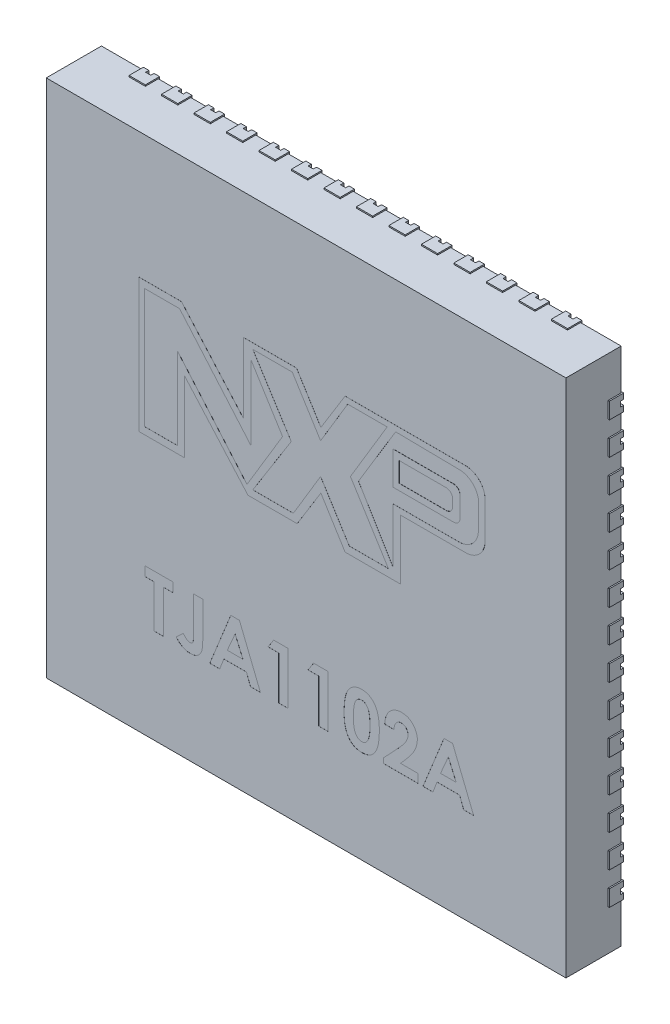
SolidWorks part; units mm, degrees
ref_plane "Front Plane" through (0, 0, 0) normal (0, 0, 1) x (1, 0, 0)
ref_plane "Top Plane" through (0, 0, 0) normal (0, 1, 0) x (1, 0, 0)
ref_plane "Right Plane" through (0, 0, 0) normal (1, 0, 0) x (0, 0, -1)
sketch "Sketch1" plane through (0, 0, 0) normal (0, 0, 1) x (1, 0, 0)
  line L1 (4, -4) -> (-4, -4)
  line L2 (4, -4) -> (4, 4)
  line L3 (4, 4) -> (-4, 4)
  line L4 (-4, -4) -> (-4, 4)
  line L5 (4, -4) -> (-4, 4) construction
  line L6 (4, 4) -> (-4, -4) construction
  point P0 (0, 0)
  dimension "D1" = 8
  dimension "D2" = 8
extrude "Boss-Extrude1" add sketch "Sketch1" along normal blind 0.85
sketch "Sketch3" plane through (0, 0, 0.85) normal (0, 0, 1) x (1, 0, 0)
  line L1 (-1.8824, 1.9808) -> (1.8824, 1.9808)
  line L2 (-1.8824, 1.9808) -> (-1.8824, -1.9808)
  line L3 (-1.8824, -1.9808) -> (1.8824, -1.9808)
  line L4 (1.8824, 1.9808) -> (1.8824, -1.9808)
  line L5 (-1.8824, 1.9808) -> (1.8824, -1.9808) construction
  line L6 (-1.8824, -1.9808) -> (1.8824, 1.9808) construction
  point P0 (0, 0)
sketch "Sketch4" plane through (0, 0, 0) normal (0, 0, -1) x (-1, 0, 0)
  line L5 (2.5, 2.25) -> (2.5, 2.1354)
  line L6 (-2.25, 2.5) -> (2.25, 2.5)
  line L11 (-2.5, 2.25) -> (-2.5, -2.25)
  line L12 (-2.25, -2.5) -> (2.25, -2.5)
  line L14 (-2.5, 2.5) -> (2.5, -2.5) construction
  line L15 (-2.5, -2.5) -> (2.5, 2.5) construction
  line L16 (2.5, 1.4646) -> (2.5, -2.25)
  arc A7 (2.25, -2.5) -> (2.5, -2.25) centre (2.25, -2.25) ccw
  arc A8 (-2.5, -2.25) -> (-2.25, -2.5) centre (-2.25, -2.25) ccw
  arc A9 (2.25, 2.5) -> (2.5, 2.25) centre (2.25, 2.25) cw
  arc A10 (-2.5, 2.25) -> (-2.25, 2.5) centre (-2.25, 2.25) cw
  arc A11 (2.4286, 2.0396) -> (2.4286, 1.5604) centre (2.5, 1.8) ccw
  arc A12 (2.5, 2.1354) -> (2.4286, 2.0396) centre (2.4, 2.1354) cw
  arc A13 (2.4286, 1.5604) -> (2.5, 1.4646) centre (2.4, 1.4646) cw
  point P0 (0, 0)
  point P23 (2.5, 2.05)
  dimension "D3" = 0.25
  dimension "D4" = 0.2
  dimension "D5" = 0.25
  dimension "D6" = 0.1
  dimension "D1" = 5
  dimension "D2" = 5
sketch "Sketch6" plane through (0, 0, 0.85) normal (0, 0, 1) x (1, 0, 0)
  line L0 (70.7212, 256.7277) -> (518.7212, 256.7277) construction
  line L1 (-2.5722, 0) -> (-2.5722, 2.0583)
  line L2 (-2.5722, 2.0583) -> (-1.9179, 2.0583)
  line L3 (-1.9179, 2.0583) -> (-0.9614, 0.9766)
  line L4 (-0.9614, 0.9766) -> (-0.9614, 2.0583)
  line L5 (-0.9614, 2.0583) -> (-0.1462, 2.0583)
  line L6 (-0.1462, 2.0583) -> (0.2284, 1.4545)
  line L7 (0.2284, 1.4545) -> (0.6013, 2.0583)
  line L8 (0.6013, 2.0583) -> (2.4559, 2.0583)
  line L9 (2.7559, 1.7583) -> (2.7559, 1.199)
  line L10 (2.4559, 0.899) -> (1.4554, 0.899)
  line L11 (1.4554, 0.899) -> (1.4554, -0.0211)
  line L12 (1.4554, -0.0211) -> (0.6013, -0.0211)
  line L13 (0.6013, -0.0211) -> (0.2284, 0.5802)
  line L14 (0.2284, 0.5802) -> (-0.1364, -0.0105)
  line L15 (-0.1364, -0.0105) -> (-0.8934, -0.0105)
  line L16 (-0.8934, -0.0105) -> (-1.8737, 1.0981)
  line L17 (-1.8737, 1.0981) -> (-1.8737, 0)
  line L18 (-1.8737, 0) -> (-2.5722, 0)
  line L19 (-2.4846, 0.1087) -> (-2.4846, 1.9505)
  line L20 (-2.4846, 1.9505) -> (-1.9464, 1.9505)
  line L21 (-1.9464, 1.9505) -> (-0.8502, 0.6771)
  line L22 (-0.8502, 0.6771) -> (-0.8502, 1.8218)
  line L23 (-0.8502, 1.8218) -> (-0.3611, 1.0381)
  line L24 (-0.3611, 1.0381) -> (-0.9093, 0.1258)
  line L25 (-0.9093, 0.1258) -> (-1.9778, 1.3671)
  line L26 (-1.9778, 1.3671) -> (-1.9778, 0.1087)
  line L27 (-1.9778, 0.1087) -> (-2.4846, 0.1087)
  line L28 (-0.8199, 1.9719) -> (-0.2112, 1.9719)
  line L29 (-0.2112, 1.9719) -> (0.224, 1.2753)
  line L30 (0.224, 1.2753) -> (0.6416, 1.9719)
  line L31 (0.6416, 1.9719) -> (1.2491, 1.9719)
  line L32 (1.2491, 1.9719) -> (0.6835, 1.0283)
  line L33 (0.6835, 1.0283) -> (1.2684, 0.092)
  line L34 (1.2684, 0.092) -> (0.6649, 0.092)
  line L35 (0.6649, 0.092) -> (0.224, 0.7978)
  line L36 (0.224, 0.7978) -> (-0.1955, 0.0981)
  line L37 (-0.1955, 0.0981) -> (-0.8199, 0.0981)
  line L38 (-0.8199, 0.0981) -> (-0.228, 1.0381)
  line L39 (-0.228, 1.0381) -> (-0.8199, 1.9719)
  line L40 (1.3791, 1.9719) -> (2.3628, 1.9581)
  line L41 (2.6586, 1.6539) -> (2.6534, 1.2867)
  line L42 (2.3534, 0.9909) -> (1.3388, 0.9909)
  line L43 (1.3388, 0.9909) -> (1.3388, 0.1474)
  line L44 (1.3388, 0.1474) -> (0.8077, 1.0283)
  line L45 (0.8077, 1.0283) -> (1.3791, 1.9719)
  line L47 (1.3388, 1.7237) -> (2.2715, 1.7237)
  line L48 (2.3715, 1.6237) -> (2.3715, 1.3142)
  line L49 (2.2715, 1.2142) -> (1.3388, 1.2142)
  line L50 (1.3388, 1.7237) -> (1.3388, 1.2142)
  line L51 (1.4343, 1.6171) -> (2.1585, 1.6171)
  line L52 (1.4343, 1.6171) -> (1.4343, 1.3132)
  line L53 (1.4343, 1.3132) -> (2.1585, 1.3132)
  line L54 (2.2585, 1.5171) -> (2.2585, 1.4132)
  arc A0 (2.7559, 1.199) -> (2.4559, 0.899) centre (2.4559, 1.199) cw
  arc A1 (2.4559, 2.0583) -> (2.7559, 1.7583) centre (2.4559, 1.7583) cw
  arc A2 (2.6534, 1.2867) -> (2.3534, 0.9909) centre (2.3534, 1.2909) cw
  arc A3 (2.3628, 1.9581) -> (2.6586, 1.6539) centre (2.3586, 1.6581) cw
  arc A4 (2.1585, 1.3132) -> (2.2585, 1.4132) centre (2.1585, 1.4132) ccw
  arc A5 (2.1585, 1.6171) -> (2.2585, 1.5171) centre (2.1585, 1.5171) cw
  arc A6 (2.3715, 1.3142) -> (2.2715, 1.2142) centre (2.2715, 1.3142) cw
  arc A7 (2.2715, 1.7237) -> (2.3715, 1.6237) centre (2.2715, 1.6237) cw
  dimension "D1" = 0.3
  dimension "D2" = 0.3
  dimension "D3" = 0.1
extrude "Boss-Extrude2" add sketch "Sketch6" along normal blind 0.001 contours A1 L8 L7 L6 L5 L4 L3 L2 L1 L18 L17 L16 L15 L14 L13 L12 L11 L10 A0 L9 L38 L39 L28 L29 L30 L31 L32 L33 L34 L35 L36 L37 L26 L27 L19 L20 L21 L22 L23 L24 L25 L40 A3 L41 A2 L42 L43 L44 | L52 L51 A5 L54 A4 L53 | L50 L49 A6 L48 A7 L47 region at (-2.515, 1.0291, 0.85)
sketch "Sketch8" plane through (0, 0, 0.85) normal (0, 0, 1) x (1, 0, 0)
  line L0 (-2.4928, -2.5446) -> (2.0877, -2.5446) construction
  text T0 "<b>TJA1102A</b>" font "Century Gothic" height 0.8
  point P3 (-2.4928, -2.6652)
extrude "Cut-Extrude3" cut sketch "Sketch8" against normal blind 0.001
sketch "Sketch10" plane through (0, 0, 0.85) normal (0, 0, 1) x (1, 0, 0)
  line L0 (1.3388, 1.7237) -> (2.2715, 1.7237)
  line L1 (1.3388, 1.7237) -> (1.3388, 1.2142)
  line L2 (1.3388, 1.2142) -> (2.2715, 1.2142)
  line L3 (2.3715, 1.6237) -> (2.3715, 1.3142)
  line L4 (2.2585, 1.5171) -> (2.2585, 1.4132)
  line L5 (2.1585, 1.6171) -> (1.4343, 1.6171)
  line L6 (1.4343, 1.6171) -> (1.4343, 1.3132)
  line L7 (1.4343, 1.3132) -> (2.1585, 1.3132)
  line L8 (1.4343, 1.6171) -> (2.1585, 1.6171) construction
  line L9 (1.4343, 1.6171) -> (2.1585, 1.6171) construction
  arc A0 (2.2715, 1.7237) -> (2.3715, 1.6237) centre (2.2715, 1.6237) cw
  arc A1 (2.3715, 1.3142) -> (2.2715, 1.2142) centre (2.2715, 1.3142) cw
  arc A2 (2.2585, 1.4132) -> (2.1585, 1.3132) centre (2.1585, 1.4132) cw
  arc A3 (2.1585, 1.6171) -> (2.2585, 1.5171) centre (2.1585, 1.5171) cw
  point P26 (1.4343, 1.6171)
extrude "Boss-Extrude3" add sketch "Sketch10" along normal blind 0.002
sketch "Sketch17" plane through (0, 4, 0) normal (0, 1, 0) x (1, 0, 0)
  line L0 (0, 0) -> (0, 0.4871) construction
  line L1 (-2.8779, -0.0822) -> (-2.775, -0.0822)
  line L2 (-2.8779, -0.0822) -> (-2.8779, -0.1355)
  line L3 (-2.8779, -0.1355) -> (-2.775, -0.1355)
  line L4 (-2.775, -0.0822) -> (-2.775, -0.1355)
  line L5 (2.775, -0.0822) -> (2.775, -0.1355)
  line L6 (2.8779, -0.1355) -> (2.775, -0.1355)
  line L7 (2.8779, -0.0822) -> (2.8779, -0.1355)
  line L8 (2.8779, -0.0822) -> (2.775, -0.0822)
extrude "Boss-Extrude7" add sketch "Sketch17" along normal blind 0.01
mirror "Mirror3" about plane through (0, 0, 0) normal (0, 1, 0) of "Boss-Extrude7"
sketch "Sketch18" plane through (-4, 0, 0) normal (-1, 0, 0) x (0, 0, 1)
  line L0 (0, 0) -> (0.2423, 0) construction
  line L1 (0.0822, -2.6954) -> (0.1355, -2.6954)
  line L2 (0.0822, -2.6954) -> (0.0822, -2.7925)
  line L3 (0.0822, -2.7925) -> (0.1355, -2.7925)
  line L4 (0.1355, -2.6954) -> (0.1355, -2.7925)
  line L5 (0.1355, 2.6954) -> (0.1355, 2.7925)
  line L6 (0.0822, 2.7925) -> (0.1355, 2.7925)
  line L7 (0.0822, 2.6954) -> (0.0822, 2.7925)
  line L8 (0.0822, 2.6954) -> (0.1355, 2.6954)
  line L9 (0.1355, 4.01) -> (0.1355, 4) construction
  line L10 (0.0822, 4.01) -> (0.0822, 4) construction
  dimension "D1" = 0
  dimension "D2" = 0
extrude "Boss-Extrude8" add sketch "Sketch18" along normal blind 0.01
mirror "Mirror4" about plane through (0, 0, 0) normal (1, 0, 0) of "Boss-Extrude8"
extrude "Boss-Extrude11" add sketch "Sketch4" along normal blind 0.02
sketch "Sketch19" plane through (0, 0, 0) normal (0, 0, -1) x (-1, 0, 0)
  line L0 (-3.25, 4.375) -> (-3.25, 3.625) construction
  line L1 (-4, 4) -> (4, 4) construction
  line L2 (-3.125, 4.375) -> (-3.125, 3.625)
  line L3 (-3.375, 4.375) -> (-3.375, 3.625)
  line L4 (-2.875, 4.375) -> (-2.875, 3.625)
  line L5 (-2.625, 4.375) -> (-2.625, 3.625)
  line L6 (-2.75, 4.375) -> (-2.75, 3.625) construction
  line L7 (-2.375, 4.375) -> (-2.375, 3.625)
  line L8 (-2.125, 4.375) -> (-2.125, 3.625)
  line L9 (-2.25, 4.375) -> (-2.25, 3.625) construction
  line L10 (-1.875, 4.375) -> (-1.875, 3.625)
  line L11 (-1.625, 4.375) -> (-1.625, 3.625)
  line L12 (-1.75, 4.375) -> (-1.75, 3.625) construction
  line L13 (-1.375, 4.375) -> (-1.375, 3.625)
  line L14 (-1.125, 4.375) -> (-1.125, 3.625)
  line L15 (-1.25, 4.375) -> (-1.25, 3.625) construction
  line L16 (-0.875, 4.375) -> (-0.875, 3.625)
  line L17 (-0.625, 4.375) -> (-0.625, 3.625)
  line L18 (-0.75, 4.375) -> (-0.75, 3.625) construction
  line L19 (-0.375, 4.375) -> (-0.375, 3.625)
  line L20 (-0.125, 4.375) -> (-0.125, 3.625)
  line L21 (-0.25, 4.375) -> (-0.25, 3.625) construction
  line L22 (0.125, 4.375) -> (0.125, 3.625)
  line L23 (0.375, 4.375) -> (0.375, 3.625)
  line L24 (0.25, 4.375) -> (0.25, 3.625) construction
  line L25 (0.625, 4.375) -> (0.625, 3.625)
  line L26 (0.875, 4.375) -> (0.875, 3.625)
  line L27 (0.75, 4.375) -> (0.75, 3.625) construction
  line L28 (1.125, 4.375) -> (1.125, 3.625)
  line L29 (1.375, 4.375) -> (1.375, 3.625)
  line L30 (1.25, 4.375) -> (1.25, 3.625) construction
  line L31 (1.625, 4.375) -> (1.625, 3.625)
  line L32 (1.875, 4.375) -> (1.875, 3.625)
  line L33 (1.75, 4.375) -> (1.75, 3.625) construction
  line L34 (2.125, 4.375) -> (2.125, 3.625)
  line L35 (2.375, 4.375) -> (2.375, 3.625)
  line L36 (2.25, 4.375) -> (2.25, 3.625) construction
  line L37 (2.625, 4.375) -> (2.625, 3.625)
  line L38 (2.875, 4.375) -> (2.875, 3.625)
  line L39 (2.75, 4.375) -> (2.75, 3.625) construction
  line L40 (3.125, 4.375) -> (3.125, 3.625)
  line L41 (3.375, 4.375) -> (3.375, 3.625)
  line L42 (3.25, 4.375) -> (3.25, 3.625) construction
  line L43 (0, 0) -> (1.75, 0) construction
  line L44 (0, 0) -> (0, 1.3207) construction
  line L45 (4.375, 3.25) -> (3.625, 3.25) construction
  line L47 (-4.375, 3.25) -> (-3.625, 3.25) construction
  line L48 (-4.375, 3.125) -> (-3.625, 3.125)
  line L49 (-4.375, 3.375) -> (-3.625, 3.375)
  line L50 (-4.375, 2.75) -> (-3.625, 2.75) construction
  line L51 (-4.375, 2.625) -> (-3.625, 2.625)
  line L52 (-4.375, 2.875) -> (-3.625, 2.875)
  line L53 (-4.375, 2.25) -> (-3.625, 2.25) construction
  line L54 (-4.375, 2.125) -> (-3.625, 2.125)
  line L55 (-4.375, 2.375) -> (-3.625, 2.375)
  line L56 (-4.375, 1.75) -> (-3.625, 1.75) construction
  line L57 (-4.375, 1.625) -> (-3.625, 1.625)
  line L58 (-4.375, 1.875) -> (-3.625, 1.875)
  line L59 (-4.375, 1.25) -> (-3.625, 1.25) construction
  line L60 (-4.375, 1.125) -> (-3.625, 1.125)
  line L61 (-4.375, 1.375) -> (-3.625, 1.375)
  line L62 (-4.375, 0.75) -> (-3.625, 0.75) construction
  line L63 (-4.375, 0.625) -> (-3.625, 0.625)
  line L64 (-4.375, 0.875) -> (-3.625, 0.875)
  line L65 (-4.375, 0.25) -> (-3.625, 0.25) construction
  line L66 (-4.375, 0.125) -> (-3.625, 0.125)
  line L67 (-4.375, 0.375) -> (-3.625, 0.375)
  line L68 (-4.375, -0.25) -> (-3.625, -0.25) construction
  line L69 (-4.375, -0.375) -> (-3.625, -0.375)
  line L70 (-4.375, -0.125) -> (-3.625, -0.125)
  line L71 (-4.375, -0.75) -> (-3.625, -0.75) construction
  line L72 (-4.375, -0.875) -> (-3.625, -0.875)
  line L73 (-4.375, -0.625) -> (-3.625, -0.625)
  line L74 (-4.375, -1.25) -> (-3.625, -1.25) construction
  line L75 (-4.375, -1.375) -> (-3.625, -1.375)
  line L76 (-4.375, -1.125) -> (-3.625, -1.125)
  line L77 (-4.375, -1.75) -> (-3.625, -1.75) construction
  line L78 (-4.375, -1.875) -> (-3.625, -1.875)
  line L79 (-4.375, -1.625) -> (-3.625, -1.625)
  line L80 (-4.375, -2.25) -> (-3.625, -2.25) construction
  line L81 (-4.375, -2.375) -> (-3.625, -2.375)
  line L82 (-4.375, -2.125) -> (-3.625, -2.125)
  line L83 (-4.375, -2.75) -> (-3.625, -2.75) construction
  line L84 (-4.375, -2.875) -> (-3.625, -2.875)
  line L85 (-4.375, -2.625) -> (-3.625, -2.625)
  line L86 (-4.375, -3.25) -> (-3.625, -3.25) construction
  line L87 (-4.375, -3.375) -> (-3.625, -3.375)
  line L88 (-4.375, -3.125) -> (-3.625, -3.125)
  line L89 (4.375, 3.125) -> (3.625, 3.125)
  line L90 (4.375, 3.375) -> (3.625, 3.375)
  line L91 (4.375, 2.75) -> (3.625, 2.75) construction
  line L92 (4.375, 2.625) -> (3.625, 2.625)
  line L93 (4.375, 2.875) -> (3.625, 2.875)
  line L94 (4.375, 2.25) -> (3.625, 2.25) construction
  line L95 (4.375, 2.125) -> (3.625, 2.125)
  line L96 (4.375, 2.375) -> (3.625, 2.375)
  line L97 (4.375, 1.75) -> (3.625, 1.75) construction
  line L98 (4.375, 1.625) -> (3.625, 1.625)
  line L99 (4.375, 1.875) -> (3.625, 1.875)
  line L100 (4.375, 1.25) -> (3.625, 1.25) construction
  line L101 (4.375, 1.125) -> (3.625, 1.125)
  line L102 (4.375, 1.375) -> (3.625, 1.375)
  line L103 (4.375, 0.75) -> (3.625, 0.75) construction
  line L104 (4.375, 0.625) -> (3.625, 0.625)
  line L105 (4.375, 0.875) -> (3.625, 0.875)
  line L106 (4.375, 0.25) -> (3.625, 0.25) construction
  line L107 (4.375, 0.125) -> (3.625, 0.125)
  line L108 (4.375, 0.375) -> (3.625, 0.375)
  line L109 (4.375, -0.25) -> (3.625, -0.25) construction
  line L110 (4.375, -0.375) -> (3.625, -0.375)
  line L111 (4.375, -0.125) -> (3.625, -0.125)
  line L112 (4.375, -0.75) -> (3.625, -0.75) construction
  line L113 (4.375, -0.875) -> (3.625, -0.875)
  line L114 (4.375, -0.625) -> (3.625, -0.625)
  line L115 (4.375, -1.25) -> (3.625, -1.25) construction
  line L116 (4.375, -1.375) -> (3.625, -1.375)
  line L117 (4.375, -1.125) -> (3.625, -1.125)
  line L118 (4.375, -1.75) -> (3.625, -1.75) construction
  line L119 (4.375, -1.875) -> (3.625, -1.875)
  line L120 (4.375, -1.625) -> (3.625, -1.625)
  line L121 (4.375, -2.25) -> (3.625, -2.25) construction
  line L122 (4.375, -2.375) -> (3.625, -2.375)
  line L123 (4.375, -2.125) -> (3.625, -2.125)
  line L124 (4.375, -2.75) -> (3.625, -2.75) construction
  line L125 (4.375, -2.875) -> (3.625, -2.875)
  line L126 (4.375, -2.625) -> (3.625, -2.625)
  line L127 (4.375, -3.25) -> (3.625, -3.25) construction
  line L128 (4.375, -3.375) -> (3.625, -3.375)
  line L129 (4.375, -3.125) -> (3.625, -3.125)
  line L130 (-3.25, -4.375) -> (-3.25, -3.625) construction
  line L131 (-3.125, -4.375) -> (-3.125, -3.625)
  line L132 (-3.375, -4.375) -> (-3.375, -3.625)
  line L133 (-2.75, -4.375) -> (-2.75, -3.625) construction
  line L134 (-2.625, -4.375) -> (-2.625, -3.625)
  line L135 (-2.875, -4.375) -> (-2.875, -3.625)
  line L136 (-2.25, -4.375) -> (-2.25, -3.625) construction
  line L137 (-2.125, -4.375) -> (-2.125, -3.625)
  line L138 (-2.375, -4.375) -> (-2.375, -3.625)
  line L139 (-1.75, -4.375) -> (-1.75, -3.625) construction
  line L140 (-1.625, -4.375) -> (-1.625, -3.625)
  line L141 (-1.875, -4.375) -> (-1.875, -3.625)
  line L142 (-1.25, -4.375) -> (-1.25, -3.625) construction
  line L143 (-1.125, -4.375) -> (-1.125, -3.625)
  line L144 (-1.375, -4.375) -> (-1.375, -3.625)
  line L145 (-0.75, -4.375) -> (-0.75, -3.625) construction
  line L146 (-0.625, -4.375) -> (-0.625, -3.625)
  line L147 (-0.875, -4.375) -> (-0.875, -3.625)
  line L148 (-0.25, -4.375) -> (-0.25, -3.625) construction
  line L149 (-0.125, -4.375) -> (-0.125, -3.625)
  line L150 (-0.375, -4.375) -> (-0.375, -3.625)
  line L151 (0.25, -4.375) -> (0.25, -3.625) construction
  line L152 (0.375, -4.375) -> (0.375, -3.625)
  line L153 (0.125, -4.375) -> (0.125, -3.625)
  line L154 (0.75, -4.375) -> (0.75, -3.625) construction
  line L155 (0.875, -4.375) -> (0.875, -3.625)
  line L156 (0.625, -4.375) -> (0.625, -3.625)
  line L157 (1.25, -4.375) -> (1.25, -3.625) construction
  line L158 (1.375, -4.375) -> (1.375, -3.625)
  line L159 (1.125, -4.375) -> (1.125, -3.625)
  line L160 (1.75, -4.375) -> (1.75, -3.625) construction
  line L161 (1.875, -4.375) -> (1.875, -3.625)
  line L162 (1.625, -4.375) -> (1.625, -3.625)
  line L163 (2.25, -4.375) -> (2.25, -3.625) construction
  line L164 (2.375, -4.375) -> (2.375, -3.625)
  line L165 (2.125, -4.375) -> (2.125, -3.625)
  line L166 (2.75, -4.375) -> (2.75, -3.625) construction
  line L167 (2.875, -4.375) -> (2.875, -3.625)
  line L168 (2.625, -4.375) -> (2.625, -3.625)
  line L169 (3.25, -4.375) -> (3.25, -3.625) construction
  line L170 (3.375, -4.375) -> (3.375, -3.625)
  line L171 (3.125, -4.375) -> (3.125, -3.625)
  arc A0 (-3.125, 4.375) -> (-3.375, 4.375) centre (-3.25, 4.375) ccw
  arc A1 (-3.375, 3.625) -> (-3.125, 3.625) centre (-3.25, 3.625) ccw
  arc A2 (-2.625, 4.375) -> (-2.875, 4.375) centre (-2.75, 4.375) ccw
  arc A3 (-2.875, 3.625) -> (-2.625, 3.625) centre (-2.75, 3.625) ccw
  arc A4 (-2.125, 4.375) -> (-2.375, 4.375) centre (-2.25, 4.375) ccw
  arc A5 (-2.375, 3.625) -> (-2.125, 3.625) centre (-2.25, 3.625) ccw
  arc A6 (-1.625, 4.375) -> (-1.875, 4.375) centre (-1.75, 4.375) ccw
  arc A7 (-1.875, 3.625) -> (-1.625, 3.625) centre (-1.75, 3.625) ccw
  arc A8 (-1.125, 4.375) -> (-1.375, 4.375) centre (-1.25, 4.375) ccw
  arc A9 (-1.375, 3.625) -> (-1.125, 3.625) centre (-1.25, 3.625) ccw
  arc A10 (-0.625, 4.375) -> (-0.875, 4.375) centre (-0.75, 4.375) ccw
  arc A11 (-0.875, 3.625) -> (-0.625, 3.625) centre (-0.75, 3.625) ccw
  arc A12 (-0.125, 4.375) -> (-0.375, 4.375) centre (-0.25, 4.375) ccw
  arc A13 (-0.375, 3.625) -> (-0.125, 3.625) centre (-0.25, 3.625) ccw
  arc A14 (0.375, 4.375) -> (0.125, 4.375) centre (0.25, 4.375) ccw
  arc A15 (0.125, 3.625) -> (0.375, 3.625) centre (0.25, 3.625) ccw
  arc A16 (0.875, 4.375) -> (0.625, 4.375) centre (0.75, 4.375) ccw
  arc A17 (0.625, 3.625) -> (0.875, 3.625) centre (0.75, 3.625) ccw
  arc A18 (1.375, 4.375) -> (1.125, 4.375) centre (1.25, 4.375) ccw
  arc A19 (1.125, 3.625) -> (1.375, 3.625) centre (1.25, 3.625) ccw
  arc A20 (1.875, 4.375) -> (1.625, 4.375) centre (1.75, 4.375) ccw
  arc A21 (1.625, 3.625) -> (1.875, 3.625) centre (1.75, 3.625) ccw
  arc A22 (2.375, 4.375) -> (2.125, 4.375) centre (2.25, 4.375) ccw
  arc A23 (2.125, 3.625) -> (2.375, 3.625) centre (2.25, 3.625) ccw
  arc A24 (2.875, 4.375) -> (2.625, 4.375) centre (2.75, 4.375) ccw
  arc A25 (2.625, 3.625) -> (2.875, 3.625) centre (2.75, 3.625) ccw
  arc A26 (3.375, 4.375) -> (3.125, 4.375) centre (3.25, 4.375) ccw
  arc A27 (3.125, 3.625) -> (3.375, 3.625) centre (3.25, 3.625) ccw
  arc A28 (-4.375, 3.125) -> (-4.375, 3.375) centre (-4.375, 3.25) cw
  arc A29 (-3.625, 3.375) -> (-3.625, 3.125) centre (-3.625, 3.25) cw
  arc A30 (-4.375, 2.625) -> (-4.375, 2.875) centre (-4.375, 2.75) cw
  arc A31 (-3.625, 2.875) -> (-3.625, 2.625) centre (-3.625, 2.75) cw
  arc A32 (-4.375, 2.125) -> (-4.375, 2.375) centre (-4.375, 2.25) cw
  arc A33 (-3.625, 2.375) -> (-3.625, 2.125) centre (-3.625, 2.25) cw
  arc A34 (-4.375, 1.625) -> (-4.375, 1.875) centre (-4.375, 1.75) cw
  arc A35 (-3.625, 1.875) -> (-3.625, 1.625) centre (-3.625, 1.75) cw
  arc A36 (-4.375, 1.125) -> (-4.375, 1.375) centre (-4.375, 1.25) cw
  arc A37 (-3.625, 1.375) -> (-3.625, 1.125) centre (-3.625, 1.25) cw
  arc A38 (-4.375, 0.625) -> (-4.375, 0.875) centre (-4.375, 0.75) cw
  arc A39 (-3.625, 0.875) -> (-3.625, 0.625) centre (-3.625, 0.75) cw
  arc A40 (-4.375, 0.125) -> (-4.375, 0.375) centre (-4.375, 0.25) cw
  arc A41 (-3.625, 0.375) -> (-3.625, 0.125) centre (-3.625, 0.25) cw
  arc A42 (-4.375, -0.375) -> (-4.375, -0.125) centre (-4.375, -0.25) cw
  arc A43 (-3.625, -0.125) -> (-3.625, -0.375) centre (-3.625, -0.25) cw
  arc A44 (-4.375, -0.875) -> (-4.375, -0.625) centre (-4.375, -0.75) cw
  arc A45 (-3.625, -0.625) -> (-3.625, -0.875) centre (-3.625, -0.75) cw
  arc A46 (-4.375, -1.375) -> (-4.375, -1.125) centre (-4.375, -1.25) cw
  arc A47 (-3.625, -1.125) -> (-3.625, -1.375) centre (-3.625, -1.25) cw
  arc A48 (-4.375, -1.875) -> (-4.375, -1.625) centre (-4.375, -1.75) cw
  arc A49 (-3.625, -1.625) -> (-3.625, -1.875) centre (-3.625, -1.75) cw
  arc A50 (-4.375, -2.375) -> (-4.375, -2.125) centre (-4.375, -2.25) cw
  arc A51 (-3.625, -2.125) -> (-3.625, -2.375) centre (-3.625, -2.25) cw
  arc A52 (-4.375, -2.875) -> (-4.375, -2.625) centre (-4.375, -2.75) cw
  arc A53 (-3.625, -2.625) -> (-3.625, -2.875) centre (-3.625, -2.75) cw
  arc A54 (-4.375, -3.375) -> (-4.375, -3.125) centre (-4.375, -3.25) cw
  arc A55 (-3.625, -3.125) -> (-3.625, -3.375) centre (-3.625, -3.25) cw
  arc A56 (4.375, 3.125) -> (4.375, 3.375) centre (4.375, 3.25) ccw
  arc A57 (3.625, 3.375) -> (3.625, 3.125) centre (3.625, 3.25) ccw
  arc A58 (4.375, 2.625) -> (4.375, 2.875) centre (4.375, 2.75) ccw
  arc A59 (3.625, 2.875) -> (3.625, 2.625) centre (3.625, 2.75) ccw
  arc A60 (4.375, 2.125) -> (4.375, 2.375) centre (4.375, 2.25) ccw
  arc A61 (3.625, 2.375) -> (3.625, 2.125) centre (3.625, 2.25) ccw
  arc A62 (4.375, 1.625) -> (4.375, 1.875) centre (4.375, 1.75) ccw
  arc A63 (3.625, 1.875) -> (3.625, 1.625) centre (3.625, 1.75) ccw
  arc A64 (4.375, 1.125) -> (4.375, 1.375) centre (4.375, 1.25) ccw
  arc A65 (3.625, 1.375) -> (3.625, 1.125) centre (3.625, 1.25) ccw
  arc A66 (4.375, 0.625) -> (4.375, 0.875) centre (4.375, 0.75) ccw
  arc A67 (3.625, 0.875) -> (3.625, 0.625) centre (3.625, 0.75) ccw
  arc A68 (4.375, 0.125) -> (4.375, 0.375) centre (4.375, 0.25) ccw
  arc A69 (3.625, 0.375) -> (3.625, 0.125) centre (3.625, 0.25) ccw
  arc A70 (4.375, -0.375) -> (4.375, -0.125) centre (4.375, -0.25) ccw
  arc A71 (3.625, -0.125) -> (3.625, -0.375) centre (3.625, -0.25) ccw
  arc A72 (4.375, -0.875) -> (4.375, -0.625) centre (4.375, -0.75) ccw
  arc A73 (3.625, -0.625) -> (3.625, -0.875) centre (3.625, -0.75) ccw
  arc A74 (4.375, -1.375) -> (4.375, -1.125) centre (4.375, -1.25) ccw
  arc A75 (3.625, -1.125) -> (3.625, -1.375) centre (3.625, -1.25) ccw
  arc A76 (4.375, -1.875) -> (4.375, -1.625) centre (4.375, -1.75) ccw
  arc A77 (3.625, -1.625) -> (3.625, -1.875) centre (3.625, -1.75) ccw
  arc A78 (4.375, -2.375) -> (4.375, -2.125) centre (4.375, -2.25) ccw
  arc A79 (3.625, -2.125) -> (3.625, -2.375) centre (3.625, -2.25) ccw
  arc A80 (4.375, -2.875) -> (4.375, -2.625) centre (4.375, -2.75) ccw
  arc A81 (3.625, -2.625) -> (3.625, -2.875) centre (3.625, -2.75) ccw
  arc A82 (4.375, -3.375) -> (4.375, -3.125) centre (4.375, -3.25) ccw
  arc A83 (3.625, -3.125) -> (3.625, -3.375) centre (3.625, -3.25) ccw
  arc A84 (-3.125, -4.375) -> (-3.375, -4.375) centre (-3.25, -4.375) cw
  arc A85 (-3.375, -3.625) -> (-3.125, -3.625) centre (-3.25, -3.625) cw
  arc A86 (-2.625, -4.375) -> (-2.875, -4.375) centre (-2.75, -4.375) cw
  arc A87 (-2.875, -3.625) -> (-2.625, -3.625) centre (-2.75, -3.625) cw
  arc A88 (-2.125, -4.375) -> (-2.375, -4.375) centre (-2.25, -4.375) cw
  arc A89 (-2.375, -3.625) -> (-2.125, -3.625) centre (-2.25, -3.625) cw
  arc A90 (-1.625, -4.375) -> (-1.875, -4.375) centre (-1.75, -4.375) cw
  arc A91 (-1.875, -3.625) -> (-1.625, -3.625) centre (-1.75, -3.625) cw
  arc A92 (-1.125, -4.375) -> (-1.375, -4.375) centre (-1.25, -4.375) cw
  arc A93 (-1.375, -3.625) -> (-1.125, -3.625) centre (-1.25, -3.625) cw
  arc A94 (-0.625, -4.375) -> (-0.875, -4.375) centre (-0.75, -4.375) cw
  arc A95 (-0.875, -3.625) -> (-0.625, -3.625) centre (-0.75, -3.625) cw
  arc A96 (-0.125, -4.375) -> (-0.375, -4.375) centre (-0.25, -4.375) cw
  arc A97 (-0.375, -3.625) -> (-0.125, -3.625) centre (-0.25, -3.625) cw
  arc A98 (0.375, -4.375) -> (0.125, -4.375) centre (0.25, -4.375) cw
  arc A99 (0.125, -3.625) -> (0.375, -3.625) centre (0.25, -3.625) cw
  arc A100 (0.875, -4.375) -> (0.625, -4.375) centre (0.75, -4.375) cw
  arc A101 (0.625, -3.625) -> (0.875, -3.625) centre (0.75, -3.625) cw
  arc A102 (1.375, -4.375) -> (1.125, -4.375) centre (1.25, -4.375) cw
  arc A103 (1.125, -3.625) -> (1.375, -3.625) centre (1.25, -3.625) cw
  arc A104 (1.875, -4.375) -> (1.625, -4.375) centre (1.75, -4.375) cw
  arc A105 (1.625, -3.625) -> (1.875, -3.625) centre (1.75, -3.625) cw
  arc A106 (2.375, -4.375) -> (2.125, -4.375) centre (2.25, -4.375) cw
  arc A107 (2.125, -3.625) -> (2.375, -3.625) centre (2.25, -3.625) cw
  arc A108 (2.875, -4.375) -> (2.625, -4.375) centre (2.75, -4.375) cw
  arc A109 (2.625, -3.625) -> (2.875, -3.625) centre (2.75, -3.625) cw
  arc A110 (3.375, -4.375) -> (3.125, -4.375) centre (3.25, -4.375) cw
  arc A111 (3.125, -3.625) -> (3.375, -3.625) centre (3.25, -3.625) cw
  point P4 (-3.25, 4)
  point P9 (-3.25, 3.5)
  point P15 (-2.75, 4)
  point P22 (-2.25, 4)
  point P29 (-1.75, 4)
  point P36 (-1.25, 4)
  point P43 (-0.75, 4)
  point P50 (-0.25, 4)
  point P57 (0.25, 4)
  point P64 (0.75, 4)
  point P71 (1.25, 4)
  point P78 (1.75, 4)
  point P85 (2.25, 4)
  point P92 (2.75, 4)
  point P99 (3.25, 4)
  point P108 (4, 3.25)
  point P112 (-4, 3.25)
  point P119 (-4, 2.75)
  point P126 (-4, 2.25)
  point P133 (-4, 1.75)
  point P140 (-4, 1.25)
  point P147 (-4, 0.75)
  point P154 (-4, 0.25)
  point P161 (-4, -0.25)
  point P168 (-4, -0.75)
  point P175 (-4, -1.25)
  point P182 (-4, -1.75)
  point P189 (-4, -2.25)
  point P196 (-4, -2.75)
  point P203 (-4, -3.25)
  point P213 (4, 2.75)
  point P220 (4, 2.25)
  point P227 (4, 1.75)
  point P234 (4, 1.25)
  point P241 (4, 0.75)
  point P248 (4, 0.25)
  point P255 (4, -0.25)
  point P262 (4, -0.75)
  point P269 (4, -1.25)
  point P276 (4, -1.75)
  point P283 (4, -2.25)
  point P290 (4, -2.75)
  point P297 (4, -3.25)
  point P304 (-3.25, -4)
  point P311 (-2.75, -4)
  point P318 (-2.25, -4)
  point P325 (-1.75, -4)
  point P332 (-1.25, -4)
  point P339 (-0.75, -4)
  point P346 (-0.25, -4)
  point P353 (0.25, -4)
  point P360 (0.75, -4)
  point P367 (1.25, -4)
  point P374 (1.75, -4)
  point P381 (2.25, -4)
  point P388 (2.75, -4)
  point P395 (3.25, -4)
  dimension "D1" = 0.25
  dimension "D2" = 0.5
  dimension "D3" = 3.25
  dimension "D4" = 14
extrude "Boss-Extrude12" add sketch "Sketch19" along normal blind 0.02
sketch "Sketch20" plane through (0, 0, 0.85) normal (0, 0, 1) x (1, 0, 0)
  line L1 (-4, 4) -> (4, 4)
  line L2 (-4, 4) -> (-4, -4)
  line L3 (-4, -4) -> (4, -4)
  line L4 (4, 4) -> (4, -4)
  line L5 (-5.8606, 5.4088) -> (5.2055, 5.4088)
  line L6 (-5.8606, 5.4088) -> (-5.8606, -5.1245)
  line L7 (-5.8606, -5.1245) -> (5.2055, -5.1245)
  line L8 (5.2055, 5.4088) -> (5.2055, -5.1245)
extrude "Cut-Extrude5" cut sketch "Sketch20" against normal blind 60.02
sketch "Sketch21" plane through (0, -4, 0) normal (0, -1, 0) x (1, 0, 0)
  line L0 (-3.125, -0.02) -> (-3.125, 0) construction
  line L1 (-3.375, -0.02) -> (-3.125, -0.02)
  line L2 (-3.375, -0.02) -> (-3.375, 0.2)
  line L3 (-3.375, 0.2) -> (-3.125, 0.2)
  line L4 (-3.125, -0.02) -> (-3.125, 0.2)
  line L5 (-3.125, 0) -> (-2.875, 0) construction
  line L6 (-2.875, -0.02) -> (-2.875, 0.2)
  line L7 (-2.875, -0.02) -> (-2.625, -0.02)
  line L8 (-2.625, -0.02) -> (-2.625, 0.2)
  line L9 (-2.875, 0.2) -> (-2.625, 0.2)
  line L10 (-2.375, -0.02) -> (-2.375, 0.2)
  line L11 (-2.375, -0.02) -> (-2.125, -0.02)
  line L12 (-2.125, -0.02) -> (-2.125, 0.2)
  line L13 (-2.375, 0.2) -> (-2.125, 0.2)
  line L14 (-1.875, -0.02) -> (-1.875, 0.2)
  line L15 (-1.875, -0.02) -> (-1.625, -0.02)
  line L16 (-1.625, -0.02) -> (-1.625, 0.2)
  line L17 (-1.875, 0.2) -> (-1.625, 0.2)
  line L18 (-1.375, -0.02) -> (-1.375, 0.2)
  line L19 (-1.375, -0.02) -> (-1.125, -0.02)
  line L20 (-1.125, -0.02) -> (-1.125, 0.2)
  line L21 (-1.375, 0.2) -> (-1.125, 0.2)
  line L22 (-0.875, -0.02) -> (-0.875, 0.2)
  line L23 (-0.875, -0.02) -> (-0.625, -0.02)
  line L24 (-0.625, -0.02) -> (-0.625, 0.2)
  line L25 (-0.875, 0.2) -> (-0.625, 0.2)
  line L26 (-0.375, -0.02) -> (-0.375, 0.2)
  line L27 (-0.375, -0.02) -> (-0.125, -0.02)
  line L28 (-0.125, -0.02) -> (-0.125, 0.2)
  line L29 (-0.375, 0.2) -> (-0.125, 0.2)
  line L30 (0.125, -0.02) -> (0.125, 0.2)
  line L31 (0.125, -0.02) -> (0.375, -0.02)
  line L32 (0.375, -0.02) -> (0.375, 0.2)
  line L33 (0.125, 0.2) -> (0.375, 0.2)
  line L34 (0.625, -0.02) -> (0.625, 0.2)
  line L35 (0.625, -0.02) -> (0.875, -0.02)
  line L36 (0.875, -0.02) -> (0.875, 0.2)
  line L37 (0.625, 0.2) -> (0.875, 0.2)
  line L38 (1.125, -0.02) -> (1.125, 0.2)
  line L39 (1.125, -0.02) -> (1.375, -0.02)
  line L40 (1.375, -0.02) -> (1.375, 0.2)
  line L41 (1.125, 0.2) -> (1.375, 0.2)
  line L42 (1.625, -0.02) -> (1.625, 0.2)
  line L43 (1.625, -0.02) -> (1.875, -0.02)
  line L44 (1.875, -0.02) -> (1.875, 0.2)
  line L45 (1.625, 0.2) -> (1.875, 0.2)
  line L46 (2.125, -0.02) -> (2.125, 0.2)
  line L47 (2.125, -0.02) -> (2.375, -0.02)
  line L48 (2.375, -0.02) -> (2.375, 0.2)
  line L49 (2.125, 0.2) -> (2.375, 0.2)
  line L50 (2.625, -0.02) -> (2.625, 0.2)
  line L51 (2.625, -0.02) -> (2.875, -0.02)
  line L52 (2.875, -0.02) -> (2.875, 0.2)
  line L53 (2.625, 0.2) -> (2.875, 0.2)
  line L54 (3.125, -0.02) -> (3.125, 0.2)
  line L55 (3.125, -0.02) -> (3.375, -0.02)
  line L56 (3.375, -0.02) -> (3.375, 0.2)
  line L57 (3.125, 0.2) -> (3.375, 0.2)
  dimension "D1" = 0
  dimension "D2" = 0.2
  dimension "D3" = 14
extrude "Boss-Extrude13" add sketch "Sketch21" along normal blind 0.02
mirror "Mirror5" about plane through (0, 0, 0) normal (0, 1, 0) of "Boss-Extrude13"
sketch "Sketch22" plane through (-4, 0, 0) normal (-1, 0, 0) x (0, 0, 1)
  line L0 (-0.02, 3.125) -> (0, 3.125) construction
  line L1 (-0.02, 3.375) -> (0.2, 3.375)
  line L2 (-0.02, 3.375) -> (-0.02, 3.125)
  line L3 (-0.02, 3.125) -> (0.2, 3.125)
  line L4 (0.2, 3.375) -> (0.2, 3.125)
  line L5 (0, 3.125) -> (0, 2.875) construction
  line L6 (-0.02, 2.875) -> (-0.02, 2.625)
  line L7 (-0.02, 2.875) -> (0.2, 2.875)
  line L8 (0.2, 2.875) -> (0.2, 2.625)
  line L9 (-0.02, 2.625) -> (0.2, 2.625)
  line L10 (-0.02, 2.375) -> (-0.02, 2.125)
  line L11 (-0.02, 2.375) -> (0.2, 2.375)
  line L12 (0.2, 2.375) -> (0.2, 2.125)
  line L13 (-0.02, 2.125) -> (0.2, 2.125)
  line L14 (-0.02, 1.875) -> (-0.02, 1.625)
  line L15 (-0.02, 1.875) -> (0.2, 1.875)
  line L16 (0.2, 1.875) -> (0.2, 1.625)
  line L17 (-0.02, 1.625) -> (0.2, 1.625)
  line L18 (-0.02, 1.375) -> (-0.02, 1.125)
  line L19 (-0.02, 1.375) -> (0.2, 1.375)
  line L20 (0.2, 1.375) -> (0.2, 1.125)
  line L21 (-0.02, 1.125) -> (0.2, 1.125)
  line L22 (-0.02, 0.875) -> (-0.02, 0.625)
  line L23 (-0.02, 0.875) -> (0.2, 0.875)
  line L24 (0.2, 0.875) -> (0.2, 0.625)
  line L25 (-0.02, 0.625) -> (0.2, 0.625)
  line L26 (-0.02, 0.375) -> (-0.02, 0.125)
  line L27 (-0.02, 0.375) -> (0.2, 0.375)
  line L28 (0.2, 0.375) -> (0.2, 0.125)
  line L29 (-0.02, 0.125) -> (0.2, 0.125)
  line L30 (-0.02, -0.125) -> (-0.02, -0.375)
  line L31 (-0.02, -0.125) -> (0.2, -0.125)
  line L32 (0.2, -0.125) -> (0.2, -0.375)
  line L33 (-0.02, -0.375) -> (0.2, -0.375)
  line L34 (-0.02, -0.625) -> (-0.02, -0.875)
  line L35 (-0.02, -0.625) -> (0.2, -0.625)
  line L36 (0.2, -0.625) -> (0.2, -0.875)
  line L37 (-0.02, -0.875) -> (0.2, -0.875)
  line L38 (-0.02, -1.1249) -> (-0.02, -1.3749)
  line L39 (-0.02, -1.1249) -> (0.2, -1.1249)
  line L40 (0.2, -1.1249) -> (0.2, -1.3749)
  line L41 (-0.02, -1.3749) -> (0.2, -1.3749)
  line L42 (-0.02, -1.6249) -> (-0.02, -1.8749)
  line L43 (-0.02, -1.6249) -> (0.2, -1.6249)
  line L44 (0.2, -1.6249) -> (0.2, -1.8749)
  line L45 (-0.02, -1.8749) -> (0.2, -1.8749)
  line L46 (-0.02, -2.1249) -> (-0.02, -2.3749)
  line L47 (-0.02, -2.1249) -> (0.2, -2.1249)
  line L48 (0.2, -2.1249) -> (0.2, -2.3749)
  line L49 (-0.02, -2.3749) -> (0.2, -2.3749)
  line L50 (-0.02, -2.6249) -> (-0.02, -2.8749)
  line L51 (-0.02, -2.6249) -> (0.2, -2.6249)
  line L52 (0.2, -2.6249) -> (0.2, -2.8749)
  line L53 (-0.02, -2.8749) -> (0.2, -2.8749)
  line L54 (-0.02, -3.1249) -> (-0.02, -3.3749)
  line L55 (-0.02, -3.1249) -> (0.2, -3.1249)
  line L56 (0.2, -3.1249) -> (0.2, -3.3749)
  line L57 (-0.02, -3.3749) -> (0.2, -3.3749)
  dimension "D1" = 0
  dimension "D2" = 0.2
  dimension "D3" = 14
extrude "Boss-Extrude14" add sketch "Sketch22" along normal blind 0.02
mirror "Mirror6" about plane through (0, 0, 0) normal (1, 0, 0) of "Boss-Extrude14"
sketch "Sketch23" plane through (0, 0, 0) normal (0, 0, -1) x (-1, 0, 0)
  line L0 (-3.375, -3.7261) -> (-3.1744, -3.5255)
  line L1 (-3.375, -3.625) -> (-3.375, -4) construction
  line L2 (-3.1744, -3.5255) -> (-3.1744, -3.402)
  line L3 (-3.1744, -3.402) -> (-3.375, -3.402)
  line L4 (-3.375, -3.402) -> (-3.375, -3.7261)
  line L5 (-4, -4) -> (-3.6526, -3.6526) construction
  line L6 (-3.375, -4) -> (-4, -4) construction
  line L7 (0, 0) -> (0, -0.7705) construction
  line L8 (0, 0) -> (-0.8048, 0) construction
  line L9 (-3.402, -3.1744) -> (-3.402, -3.375)
  line L10 (-3.5255, -3.1744) -> (-3.402, -3.1744)
  line L11 (-3.7261, -3.375) -> (-3.5255, -3.1744)
  line L12 (-3.402, -3.375) -> (-3.7261, -3.375)
  line L13 (3.5255, -3.1744) -> (3.402, -3.1744)
  line L14 (3.7261, -3.375) -> (3.5255, -3.1744)
  line L15 (3.402, -3.375) -> (3.7261, -3.375)
  line L16 (3.402, -3.1744) -> (3.402, -3.375)
  line L17 (3.1744, -3.402) -> (3.375, -3.402)
  line L18 (3.1744, -3.5255) -> (3.1744, -3.402)
  line L19 (3.375, -3.7261) -> (3.1744, -3.5255)
  line L20 (3.375, -3.402) -> (3.375, -3.7261)
  line L21 (3.1744, 3.5255) -> (3.1744, 3.402)
  line L22 (3.375, 3.7261) -> (3.1744, 3.5255)
  line L23 (3.375, 3.402) -> (3.375, 3.7261)
  line L24 (3.1744, 3.402) -> (3.375, 3.402)
  line L25 (3.7261, 3.375) -> (3.5255, 3.1744)
  line L26 (3.402, 3.375) -> (3.7261, 3.375)
  line L27 (3.402, 3.1744) -> (3.402, 3.375)
  line L28 (3.5255, 3.1744) -> (3.402, 3.1744)
  line L29 (-3.1744, 3.402) -> (-3.375, 3.402)
  line L30 (-3.1744, 3.5255) -> (-3.1744, 3.402)
  line L31 (-3.375, 3.7261) -> (-3.1744, 3.5255)
  line L32 (-3.375, 3.402) -> (-3.375, 3.7261)
  line L33 (-3.5255, 3.1744) -> (-3.402, 3.1744)
  line L34 (-3.7261, 3.375) -> (-3.5255, 3.1744)
  line L35 (-3.402, 3.375) -> (-3.7261, 3.375)
  line L36 (-3.402, 3.1744) -> (-3.402, 3.375)
  arc A0 (-3.125, -3.625) -> (-3.375, -3.625) centre (-3.25, -3.625) ccw construction
  dimension "D1" = 45
extrude "Cut-Extrude6" cut sketch "Sketch23" along normal blind 30.02
sketch "Sketch24" plane through (0, 0, -0.02) normal (0, 0, -1) x (-1, 0, 0)
  line L0 (-3.25, -4.06) -> (-3.25, -3.98) construction
  line L1 (-3.125, -4.02) -> (-3.375, -4.02) construction
  line L2 (-3.29, -4.06) -> (-3.29, -3.98)
  line L3 (-3.21, -4.06) -> (-3.21, -3.98)
  line L4 (-2.71, -4.06) -> (-2.71, -3.98)
  line L5 (-2.79, -4.06) -> (-2.79, -3.98)
  line L6 (-2.75, -4.06) -> (-2.75, -3.98) construction
  line L7 (-2.21, -4.06) -> (-2.21, -3.98)
  line L8 (-2.29, -4.06) -> (-2.29, -3.98)
  line L9 (-2.25, -4.06) -> (-2.25, -3.98) construction
  line L10 (-1.71, -4.06) -> (-1.71, -3.98)
  line L11 (-1.79, -4.06) -> (-1.79, -3.98)
  line L12 (-1.75, -4.06) -> (-1.75, -3.98) construction
  line L13 (-1.21, -4.06) -> (-1.21, -3.98)
  line L14 (-1.29, -4.06) -> (-1.29, -3.98)
  line L15 (-1.25, -4.06) -> (-1.25, -3.98) construction
  line L16 (-0.71, -4.06) -> (-0.71, -3.98)
  line L17 (-0.79, -4.06) -> (-0.79, -3.98)
  line L18 (-0.75, -4.06) -> (-0.75, -3.98) construction
  line L19 (-0.21, -4.06) -> (-0.21, -3.98)
  line L20 (-0.29, -4.06) -> (-0.29, -3.98)
  line L21 (-0.25, -4.06) -> (-0.25, -3.98) construction
  line L22 (0.29, -4.06) -> (0.29, -3.98)
  line L23 (0.21, -4.06) -> (0.21, -3.98)
  line L24 (0.25, -4.06) -> (0.25, -3.98) construction
  line L25 (0.79, -4.06) -> (0.79, -3.98)
  line L26 (0.71, -4.06) -> (0.71, -3.98)
  line L27 (0.75, -4.06) -> (0.75, -3.98) construction
  line L28 (1.29, -4.06) -> (1.29, -3.98)
  line L29 (1.21, -4.06) -> (1.21, -3.98)
  line L30 (1.25, -4.06) -> (1.25, -3.98) construction
  line L31 (1.79, -4.06) -> (1.79, -3.98)
  line L32 (1.71, -4.06) -> (1.71, -3.98)
  line L33 (1.75, -4.06) -> (1.75, -3.98) construction
  line L34 (2.29, -4.06) -> (2.29, -3.98)
  line L35 (2.21, -4.06) -> (2.21, -3.98)
  line L36 (2.25, -4.06) -> (2.25, -3.98) construction
  line L37 (2.79, -4.06) -> (2.79, -3.98)
  line L38 (2.71, -4.06) -> (2.71, -3.98)
  line L39 (2.75, -4.06) -> (2.75, -3.98) construction
  line L40 (3.29, -4.06) -> (3.29, -3.98)
  line L41 (3.21, -4.06) -> (3.21, -3.98)
  line L42 (3.25, -4.06) -> (3.25, -3.98) construction
  line L43 (0, 0) -> (0, 1.0965) construction
  line L45 (-4.06, -3.25) -> (-3.98, -3.25) construction
  line L46 (-4.06, -3.29) -> (-3.98, -3.29)
  line L47 (-4.06, -3.21) -> (-3.98, -3.21)
  line L48 (-4.06, -2.75) -> (-3.98, -2.75) construction
  line L49 (-4.06, -2.79) -> (-3.98, -2.79)
  line L50 (-4.06, -2.71) -> (-3.98, -2.71)
  line L51 (-4.06, -2.25) -> (-3.98, -2.25) construction
  line L52 (-4.06, -2.29) -> (-3.98, -2.29)
  line L53 (-4.06, -2.21) -> (-3.98, -2.21)
  line L54 (-4.06, -1.75) -> (-3.98, -1.75) construction
  line L55 (-4.06, -1.79) -> (-3.98, -1.79)
  line L56 (-4.06, -1.71) -> (-3.98, -1.71)
  line L57 (-4.06, -1.25) -> (-3.98, -1.25) construction
  line L58 (-4.06, -1.29) -> (-3.98, -1.29)
  line L59 (-4.06, -1.21) -> (-3.98, -1.21)
  line L60 (-4.06, -0.75) -> (-3.98, -0.75) construction
  line L61 (-4.06, -0.79) -> (-3.98, -0.79)
  line L62 (-4.06, -0.71) -> (-3.98, -0.71)
  line L63 (-4.06, -0.25) -> (-3.98, -0.25) construction
  line L64 (-4.06, -0.29) -> (-3.98, -0.29)
  line L65 (-4.06, -0.21) -> (-3.98, -0.21)
  line L66 (-4.06, 0.25) -> (-3.98, 0.25) construction
  line L67 (-4.06, 0.21) -> (-3.98, 0.21)
  line L68 (-4.06, 0.29) -> (-3.98, 0.29)
  line L69 (-4.06, 0.75) -> (-3.98, 0.75) construction
  line L70 (-4.06, 0.71) -> (-3.98, 0.71)
  line L71 (-4.06, 0.79) -> (-3.98, 0.79)
  line L72 (-4.06, 1.25) -> (-3.98, 1.25) construction
  line L73 (-4.06, 1.21) -> (-3.98, 1.21)
  line L74 (-4.06, 1.29) -> (-3.98, 1.29)
  line L75 (-4.06, 1.75) -> (-3.98, 1.75) construction
  line L76 (-4.06, 1.71) -> (-3.98, 1.71)
  line L77 (-4.06, 1.79) -> (-3.98, 1.79)
  line L78 (-4.06, 2.25) -> (-3.98, 2.25) construction
  line L79 (-4.06, 2.21) -> (-3.98, 2.21)
  line L80 (-4.06, 2.29) -> (-3.98, 2.29)
  line L81 (-4.06, 2.75) -> (-3.98, 2.75) construction
  line L82 (-4.06, 2.71) -> (-3.98, 2.71)
  line L83 (-4.06, 2.79) -> (-3.98, 2.79)
  line L84 (-4.06, 3.25) -> (-3.98, 3.25) construction
  line L85 (-4.06, 3.21) -> (-3.98, 3.21)
  line L86 (-4.06, 3.29) -> (-3.98, 3.29)
  line L87 (0, 0) -> (1.21, 0) construction
  line L88 (4.06, -3.25) -> (3.98, -3.25) construction
  line L89 (4.06, -3.29) -> (3.98, -3.29)
  line L90 (4.06, -3.21) -> (3.98, -3.21)
  line L91 (4.06, -2.75) -> (3.98, -2.75) construction
  line L92 (4.06, -2.79) -> (3.98, -2.79)
  line L93 (4.06, -2.71) -> (3.98, -2.71)
  line L94 (4.06, -2.25) -> (3.98, -2.25) construction
  line L95 (4.06, -2.29) -> (3.98, -2.29)
  line L96 (4.06, -2.21) -> (3.98, -2.21)
  line L97 (4.06, -1.75) -> (3.98, -1.75) construction
  line L98 (4.06, -1.79) -> (3.98, -1.79)
  line L99 (4.06, -1.71) -> (3.98, -1.71)
  line L100 (4.06, -1.25) -> (3.98, -1.25) construction
  line L101 (4.06, -1.29) -> (3.98, -1.29)
  line L102 (4.06, -1.21) -> (3.98, -1.21)
  line L103 (4.06, -0.75) -> (3.98, -0.75) construction
  line L104 (4.06, -0.79) -> (3.98, -0.79)
  line L105 (4.06, -0.71) -> (3.98, -0.71)
  line L106 (4.06, -0.25) -> (3.98, -0.25) construction
  line L107 (4.06, -0.29) -> (3.98, -0.29)
  line L108 (4.06, -0.21) -> (3.98, -0.21)
  line L109 (4.06, 0.25) -> (3.98, 0.25) construction
  line L110 (4.06, 0.21) -> (3.98, 0.21)
  line L111 (4.06, 0.29) -> (3.98, 0.29)
  line L112 (4.06, 0.75) -> (3.98, 0.75) construction
  line L113 (4.06, 0.71) -> (3.98, 0.71)
  line L114 (4.06, 0.79) -> (3.98, 0.79)
  line L115 (4.06, 1.25) -> (3.98, 1.25) construction
  line L116 (4.06, 1.21) -> (3.98, 1.21)
  line L117 (4.06, 1.29) -> (3.98, 1.29)
  line L118 (4.06, 1.75) -> (3.98, 1.75) construction
  line L119 (4.06, 1.71) -> (3.98, 1.71)
  line L120 (4.06, 1.79) -> (3.98, 1.79)
  line L121 (4.06, 2.25) -> (3.98, 2.25) construction
  line L122 (4.06, 2.21) -> (3.98, 2.21)
  line L123 (4.06, 2.29) -> (3.98, 2.29)
  line L124 (4.06, 2.75) -> (3.98, 2.75) construction
  line L125 (4.06, 2.71) -> (3.98, 2.71)
  line L126 (4.06, 2.79) -> (3.98, 2.79)
  line L127 (4.06, 3.25) -> (3.98, 3.25) construction
  line L128 (4.06, 3.21) -> (3.98, 3.21)
  line L129 (4.06, 3.29) -> (3.98, 3.29)
  line L130 (3.25, 4.06) -> (3.25, 3.98) construction
  line L131 (3.21, 4.06) -> (3.21, 3.98)
  line L132 (3.29, 4.06) -> (3.29, 3.98)
  line L133 (2.75, 4.06) -> (2.75, 3.98) construction
  line L134 (2.71, 4.06) -> (2.71, 3.98)
  line L135 (2.79, 4.06) -> (2.79, 3.98)
  line L136 (2.25, 4.06) -> (2.25, 3.98) construction
  line L137 (2.21, 4.06) -> (2.21, 3.98)
  line L138 (2.29, 4.06) -> (2.29, 3.98)
  line L139 (1.75, 4.06) -> (1.75, 3.98) construction
  line L140 (1.71, 4.06) -> (1.71, 3.98)
  line L141 (1.79, 4.06) -> (1.79, 3.98)
  line L142 (1.25, 4.06) -> (1.25, 3.98) construction
  line L143 (1.21, 4.06) -> (1.21, 3.98)
  line L144 (1.29, 4.06) -> (1.29, 3.98)
  line L145 (0.75, 4.06) -> (0.75, 3.98) construction
  line L146 (0.71, 4.06) -> (0.71, 3.98)
  line L147 (0.79, 4.06) -> (0.79, 3.98)
  line L148 (0.25, 4.06) -> (0.25, 3.98) construction
  line L149 (0.21, 4.06) -> (0.21, 3.98)
  line L150 (0.29, 4.06) -> (0.29, 3.98)
  line L151 (-0.25, 4.06) -> (-0.25, 3.98) construction
  line L152 (-0.29, 4.06) -> (-0.29, 3.98)
  line L153 (-0.21, 4.06) -> (-0.21, 3.98)
  line L154 (-0.75, 4.06) -> (-0.75, 3.98) construction
  line L155 (-0.79, 4.06) -> (-0.79, 3.98)
  line L156 (-0.71, 4.06) -> (-0.71, 3.98)
  line L157 (-1.25, 4.06) -> (-1.25, 3.98) construction
  line L158 (-1.29, 4.06) -> (-1.29, 3.98)
  line L159 (-1.21, 4.06) -> (-1.21, 3.98)
  line L160 (-1.75, 4.06) -> (-1.75, 3.98) construction
  line L161 (-1.79, 4.06) -> (-1.79, 3.98)
  line L162 (-1.71, 4.06) -> (-1.71, 3.98)
  line L163 (-2.25, 4.06) -> (-2.25, 3.98) construction
  line L164 (-2.29, 4.06) -> (-2.29, 3.98)
  line L165 (-2.21, 4.06) -> (-2.21, 3.98)
  line L166 (-2.75, 4.06) -> (-2.75, 3.98) construction
  line L167 (-2.79, 4.06) -> (-2.79, 3.98)
  line L168 (-2.71, 4.06) -> (-2.71, 3.98)
  line L169 (-3.25, 4.06) -> (-3.25, 3.98) construction
  line L170 (-3.29, 4.06) -> (-3.29, 3.98)
  line L171 (-3.21, 4.06) -> (-3.21, 3.98)
  arc A0 (-3.29, -4.06) -> (-3.21, -4.06) centre (-3.25, -4.06) ccw
  arc A1 (-3.21, -3.98) -> (-3.29, -3.98) centre (-3.25, -3.98) ccw
  arc A2 (-2.79, -4.06) -> (-2.71, -4.06) centre (-2.75, -4.06) ccw
  arc A3 (-2.71, -3.98) -> (-2.79, -3.98) centre (-2.75, -3.98) ccw
  arc A4 (-2.29, -4.06) -> (-2.21, -4.06) centre (-2.25, -4.06) ccw
  arc A5 (-2.21, -3.98) -> (-2.29, -3.98) centre (-2.25, -3.98) ccw
  arc A6 (-1.79, -4.06) -> (-1.71, -4.06) centre (-1.75, -4.06) ccw
  arc A7 (-1.71, -3.98) -> (-1.79, -3.98) centre (-1.75, -3.98) ccw
  arc A8 (-1.29, -4.06) -> (-1.21, -4.06) centre (-1.25, -4.06) ccw
  arc A9 (-1.21, -3.98) -> (-1.29, -3.98) centre (-1.25, -3.98) ccw
  arc A10 (-0.79, -4.06) -> (-0.71, -4.06) centre (-0.75, -4.06) ccw
  arc A11 (-0.71, -3.98) -> (-0.79, -3.98) centre (-0.75, -3.98) ccw
  arc A12 (-0.29, -4.06) -> (-0.21, -4.06) centre (-0.25, -4.06) ccw
  arc A13 (-0.21, -3.98) -> (-0.29, -3.98) centre (-0.25, -3.98) ccw
  arc A14 (0.21, -4.06) -> (0.29, -4.06) centre (0.25, -4.06) ccw
  arc A15 (0.29, -3.98) -> (0.21, -3.98) centre (0.25, -3.98) ccw
  arc A16 (0.71, -4.06) -> (0.79, -4.06) centre (0.75, -4.06) ccw
  arc A17 (0.79, -3.98) -> (0.71, -3.98) centre (0.75, -3.98) ccw
  arc A18 (1.21, -4.06) -> (1.29, -4.06) centre (1.25, -4.06) ccw
  arc A19 (1.29, -3.98) -> (1.21, -3.98) centre (1.25, -3.98) ccw
  arc A20 (1.71, -4.06) -> (1.79, -4.06) centre (1.75, -4.06) ccw
  arc A21 (1.79, -3.98) -> (1.71, -3.98) centre (1.75, -3.98) ccw
  arc A22 (2.21, -4.06) -> (2.29, -4.06) centre (2.25, -4.06) ccw
  arc A23 (2.29, -3.98) -> (2.21, -3.98) centre (2.25, -3.98) ccw
  arc A24 (2.71, -4.06) -> (2.79, -4.06) centre (2.75, -4.06) ccw
  arc A25 (2.79, -3.98) -> (2.71, -3.98) centre (2.75, -3.98) ccw
  arc A26 (3.21, -4.06) -> (3.29, -4.06) centre (3.25, -4.06) ccw
  arc A27 (3.29, -3.98) -> (3.21, -3.98) centre (3.25, -3.98) ccw
  arc A28 (-4.06, -3.29) -> (-4.06, -3.21) centre (-4.06, -3.25) cw
  arc A29 (-3.98, -3.21) -> (-3.98, -3.29) centre (-3.98, -3.25) cw
  arc A30 (-4.06, -2.79) -> (-4.06, -2.71) centre (-4.06, -2.75) cw
  arc A31 (-3.98, -2.71) -> (-3.98, -2.79) centre (-3.98, -2.75) cw
  arc A32 (-4.06, -2.29) -> (-4.06, -2.21) centre (-4.06, -2.25) cw
  arc A33 (-3.98, -2.21) -> (-3.98, -2.29) centre (-3.98, -2.25) cw
  arc A34 (-4.06, -1.79) -> (-4.06, -1.71) centre (-4.06, -1.75) cw
  arc A35 (-3.98, -1.71) -> (-3.98, -1.79) centre (-3.98, -1.75) cw
  arc A36 (-4.06, -1.29) -> (-4.06, -1.21) centre (-4.06, -1.25) cw
  arc A37 (-3.98, -1.21) -> (-3.98, -1.29) centre (-3.98, -1.25) cw
  arc A38 (-4.06, -0.79) -> (-4.06, -0.71) centre (-4.06, -0.75) cw
  arc A39 (-3.98, -0.71) -> (-3.98, -0.79) centre (-3.98, -0.75) cw
  arc A40 (-4.06, -0.29) -> (-4.06, -0.21) centre (-4.06, -0.25) cw
  arc A41 (-3.98, -0.21) -> (-3.98, -0.29) centre (-3.98, -0.25) cw
  arc A42 (-4.06, 0.21) -> (-4.06, 0.29) centre (-4.06, 0.25) cw
  arc A43 (-3.98, 0.29) -> (-3.98, 0.21) centre (-3.98, 0.25) cw
  arc A44 (-4.06, 0.71) -> (-4.06, 0.79) centre (-4.06, 0.75) cw
  arc A45 (-3.98, 0.79) -> (-3.98, 0.71) centre (-3.98, 0.75) cw
  arc A46 (-4.06, 1.21) -> (-4.06, 1.29) centre (-4.06, 1.25) cw
  arc A47 (-3.98, 1.29) -> (-3.98, 1.21) centre (-3.98, 1.25) cw
  arc A48 (-4.06, 1.71) -> (-4.06, 1.79) centre (-4.06, 1.75) cw
  arc A49 (-3.98, 1.79) -> (-3.98, 1.71) centre (-3.98, 1.75) cw
  arc A50 (-4.06, 2.21) -> (-4.06, 2.29) centre (-4.06, 2.25) cw
  arc A51 (-3.98, 2.29) -> (-3.98, 2.21) centre (-3.98, 2.25) cw
  arc A52 (-4.06, 2.71) -> (-4.06, 2.79) centre (-4.06, 2.75) cw
  arc A53 (-3.98, 2.79) -> (-3.98, 2.71) centre (-3.98, 2.75) cw
  arc A54 (-4.06, 3.21) -> (-4.06, 3.29) centre (-4.06, 3.25) cw
  arc A55 (-3.98, 3.29) -> (-3.98, 3.21) centre (-3.98, 3.25) cw
  arc A56 (4.06, -3.29) -> (4.06, -3.21) centre (4.06, -3.25) ccw
  arc A57 (3.98, -3.21) -> (3.98, -3.29) centre (3.98, -3.25) ccw
  arc A58 (4.06, -2.79) -> (4.06, -2.71) centre (4.06, -2.75) ccw
  arc A59 (3.98, -2.71) -> (3.98, -2.79) centre (3.98, -2.75) ccw
  arc A60 (4.06, -2.29) -> (4.06, -2.21) centre (4.06, -2.25) ccw
  arc A61 (3.98, -2.21) -> (3.98, -2.29) centre (3.98, -2.25) ccw
  arc A62 (4.06, -1.79) -> (4.06, -1.71) centre (4.06, -1.75) ccw
  arc A63 (3.98, -1.71) -> (3.98, -1.79) centre (3.98, -1.75) ccw
  arc A64 (4.06, -1.29) -> (4.06, -1.21) centre (4.06, -1.25) ccw
  arc A65 (3.98, -1.21) -> (3.98, -1.29) centre (3.98, -1.25) ccw
  arc A66 (4.06, -0.79) -> (4.06, -0.71) centre (4.06, -0.75) ccw
  arc A67 (3.98, -0.71) -> (3.98, -0.79) centre (3.98, -0.75) ccw
  arc A68 (4.06, -0.29) -> (4.06, -0.21) centre (4.06, -0.25) ccw
  arc A69 (3.98, -0.21) -> (3.98, -0.29) centre (3.98, -0.25) ccw
  arc A70 (4.06, 0.21) -> (4.06, 0.29) centre (4.06, 0.25) ccw
  arc A71 (3.98, 0.29) -> (3.98, 0.21) centre (3.98, 0.25) ccw
  arc A72 (4.06, 0.71) -> (4.06, 0.79) centre (4.06, 0.75) ccw
  arc A73 (3.98, 0.79) -> (3.98, 0.71) centre (3.98, 0.75) ccw
  arc A74 (4.06, 1.21) -> (4.06, 1.29) centre (4.06, 1.25) ccw
  arc A75 (3.98, 1.29) -> (3.98, 1.21) centre (3.98, 1.25) ccw
  arc A76 (4.06, 1.71) -> (4.06, 1.79) centre (4.06, 1.75) ccw
  arc A77 (3.98, 1.79) -> (3.98, 1.71) centre (3.98, 1.75) ccw
  arc A78 (4.06, 2.21) -> (4.06, 2.29) centre (4.06, 2.25) ccw
  arc A79 (3.98, 2.29) -> (3.98, 2.21) centre (3.98, 2.25) ccw
  arc A80 (4.06, 2.71) -> (4.06, 2.79) centre (4.06, 2.75) ccw
  arc A81 (3.98, 2.79) -> (3.98, 2.71) centre (3.98, 2.75) ccw
  arc A82 (4.06, 3.21) -> (4.06, 3.29) centre (4.06, 3.25) ccw
  arc A83 (3.98, 3.29) -> (3.98, 3.21) centre (3.98, 3.25) ccw
  arc A84 (3.21, 4.06) -> (3.29, 4.06) centre (3.25, 4.06) cw
  arc A85 (3.29, 3.98) -> (3.21, 3.98) centre (3.25, 3.98) cw
  arc A86 (2.71, 4.06) -> (2.79, 4.06) centre (2.75, 4.06) cw
  arc A87 (2.79, 3.98) -> (2.71, 3.98) centre (2.75, 3.98) cw
  arc A88 (2.21, 4.06) -> (2.29, 4.06) centre (2.25, 4.06) cw
  arc A89 (2.29, 3.98) -> (2.21, 3.98) centre (2.25, 3.98) cw
  arc A90 (1.71, 4.06) -> (1.79, 4.06) centre (1.75, 4.06) cw
  arc A91 (1.79, 3.98) -> (1.71, 3.98) centre (1.75, 3.98) cw
  arc A92 (1.21, 4.06) -> (1.29, 4.06) centre (1.25, 4.06) cw
  arc A93 (1.29, 3.98) -> (1.21, 3.98) centre (1.25, 3.98) cw
  arc A94 (0.71, 4.06) -> (0.79, 4.06) centre (0.75, 4.06) cw
  arc A95 (0.79, 3.98) -> (0.71, 3.98) centre (0.75, 3.98) cw
  arc A96 (0.21, 4.06) -> (0.29, 4.06) centre (0.25, 4.06) cw
  arc A97 (0.29, 3.98) -> (0.21, 3.98) centre (0.25, 3.98) cw
  arc A98 (-0.29, 4.06) -> (-0.21, 4.06) centre (-0.25, 4.06) cw
  arc A99 (-0.21, 3.98) -> (-0.29, 3.98) centre (-0.25, 3.98) cw
  arc A100 (-0.79, 4.06) -> (-0.71, 4.06) centre (-0.75, 4.06) cw
  arc A101 (-0.71, 3.98) -> (-0.79, 3.98) centre (-0.75, 3.98) cw
  arc A102 (-1.29, 4.06) -> (-1.21, 4.06) centre (-1.25, 4.06) cw
  arc A103 (-1.21, 3.98) -> (-1.29, 3.98) centre (-1.25, 3.98) cw
  arc A104 (-1.79, 4.06) -> (-1.71, 4.06) centre (-1.75, 4.06) cw
  arc A105 (-1.71, 3.98) -> (-1.79, 3.98) centre (-1.75, 3.98) cw
  arc A106 (-2.29, 4.06) -> (-2.21, 4.06) centre (-2.25, 4.06) cw
  arc A107 (-2.21, 3.98) -> (-2.29, 3.98) centre (-2.25, 3.98) cw
  arc A108 (-2.79, 4.06) -> (-2.71, 4.06) centre (-2.75, 4.06) cw
  arc A109 (-2.71, 3.98) -> (-2.79, 3.98) centre (-2.75, 3.98) cw
  arc A110 (-3.29, 4.06) -> (-3.21, 4.06) centre (-3.25, 4.06) cw
  arc A111 (-3.21, 3.98) -> (-3.29, 3.98) centre (-3.25, 3.98) cw
  point P4 (-3.25, -4.02)
  point P12 (-2.75, -4.02)
  point P19 (-2.25, -4.02)
  point P26 (-1.75, -4.02)
  point P33 (-1.25, -4.02)
  point P40 (-0.75, -4.02)
  point P47 (-0.25, -4.02)
  point P54 (0.25, -4.02)
  point P61 (0.75, -4.02)
  point P68 (1.25, -4.02)
  point P75 (1.75, -4.02)
  point P82 (2.25, -4.02)
  point P89 (2.75, -4.02)
  point P96 (3.25, -4.02)
  point P107 (-4.02, -3.25)
  point P114 (-4.02, -2.75)
  point P121 (-4.02, -2.25)
  point P128 (-4.02, -1.75)
  point P135 (-4.02, -1.25)
  point P142 (-4.02, -0.75)
  point P149 (-4.02, -0.25)
  point P156 (-4.02, 0.25)
  point P163 (-4.02, 0.75)
  point P170 (-4.02, 1.25)
  point P177 (-4.02, 1.75)
  point P184 (-4.02, 2.25)
  point P191 (-4.02, 2.75)
  point P198 (-4.02, 3.25)
  point P205 (4.02, -3.25)
  point P212 (4.02, -2.75)
  point P219 (4.02, -2.25)
  point P226 (4.02, -1.75)
  point P233 (4.02, -1.25)
  point P240 (4.02, -0.75)
  point P247 (4.02, -0.25)
  point P254 (4.02, 0.25)
  point P261 (4.02, 0.75)
  point P268 (4.02, 1.25)
  point P275 (4.02, 1.75)
  point P282 (4.02, 2.25)
  point P289 (4.02, 2.75)
  point P296 (4.02, 3.25)
  point P303 (3.25, 4.02)
  point P310 (2.75, 4.02)
  point P317 (2.25, 4.02)
  point P324 (1.75, 4.02)
  point P331 (1.25, 4.02)
  point P338 (0.75, 4.02)
  point P345 (0.25, 4.02)
  point P352 (-0.25, 4.02)
  point P359 (-0.75, 4.02)
  point P366 (-1.25, 4.02)
  point P373 (-1.75, 4.02)
  point P380 (-2.25, 4.02)
  point P387 (-2.75, 4.02)
  point P394 (-3.25, 4.02)
  dimension "D2" = 0.04
  dimension "D1" = 0.04
  dimension "D3" = 14
extrude "Cut-Extrude7" cut sketch "Sketch24" against normal blind 0.05
